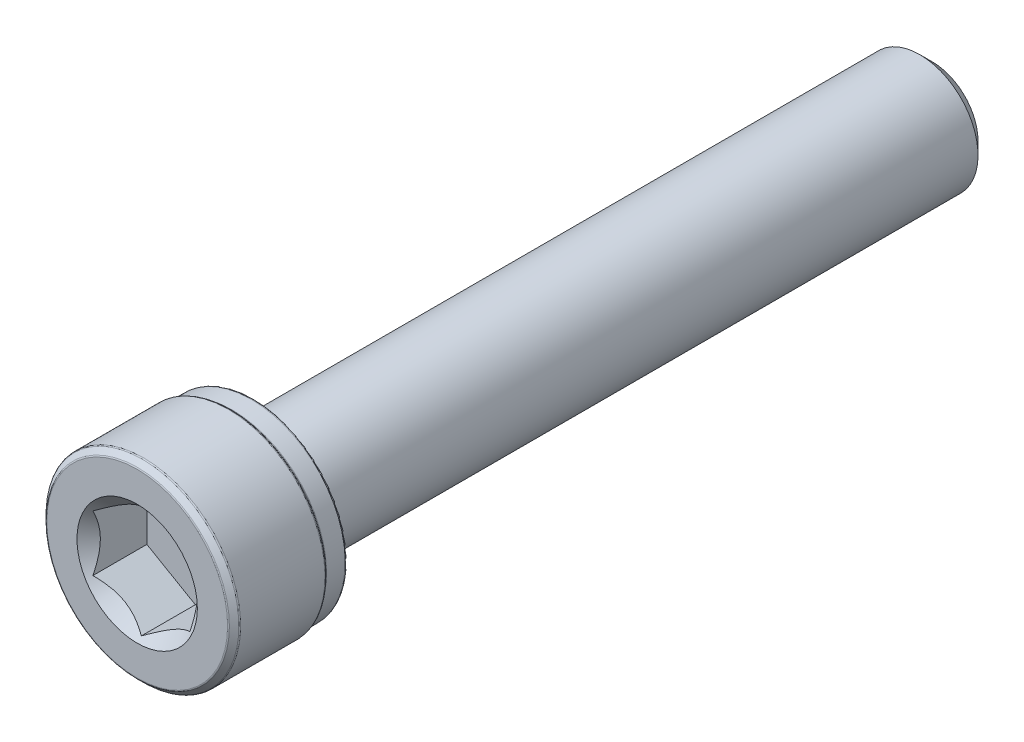
SolidWorks part; units mm, degrees
ref_plane "Front Plane" through (0, 0, 0) normal (0, 0, 1) x (1, 0, 0)
ref_plane "Top Plane" through (0, 0, 0) normal (0, 1, 0) x (1, 0, 0)
ref_plane "Right Plane" through (0, 0, 0) normal (1, 0, 0) x (0, 0, -1)
sketch "Sketch1" plane through (0, 0, 0) normal (1, 0, 0) x (0, 0, -1)
  line L0 (-20.5, 0) -> (20.5, 0) construction
  line L1 (20.5, 0) -> (20.5, 2.3505) construction
  line L2 (20.5, 2.3505) -> (19.8505, 3) construction
  line L3 (19.8505, 3) -> (19.75, 3) construction
  line L4 (19.75, 3) -> (-14.5, 3) construction
  line L5 (-14.5, 3) -> (-14.5, 5) construction
  line L6 (-14.5, 5) -> (-20.5, 5) construction
  line L7 (-20.5, 5) -> (-20.5, 0) construction
  line L8 (20.5, 2.3505) -> (20.5, 3) construction
  line L9 (20.4375, 3.1083) -> (20.9375, 2.2422) construction
  line L10 (20.9375, 2.2422) -> (21.4375, 3.1083) construction
  line L11 (21.4375, 3.1083) -> (20.4375, 3.1083) construction
  line L12 (20.9375, 3.1083) -> (20.9375, 3) construction
  line L13 (20.9375, 2.2422) -> (20.9375, 2.3505) construction
  line L14 (20.875, 2.3505) -> (21, 2.3505) construction
  line L15 (20.5, 3) -> (21.375, 3) construction
  line L16 (20.4688, 3.0541) -> (21.4062, 3.0541) construction
  line L17 (20.5, 0) -> (20.5, -3) construction
  line L18 (-14.8, 5) -> (-14.5, 4.7) construction
  line L19 (-20.2, 5) -> (-20.5, 4.7) construction
  line L20 (-14.5, 3) -> (-14.5, 0) construction
  line L21 (-14.5, 1.5) -> (-2.8333, 1.5) construction
  line L22 (-2.8333, 1.5) -> (8.8333, 1.5) construction
  line L23 (8.8333, 1.5) -> (20.5, 1.5) construction
  line L24 (-2.8333, 1.5) -> (-2.8333, 3) construction
  line L25 (-2.8333, 3) -> (-2.8333, 5) construction
  line L26 (8.8333, 1.5) -> (8.8333, 5) construction
  point P0 (-20.5, 2.5)
  point P3 (18, 3)
  point P4 (0, 0)
  point P18 (8.8333, 3)
  point P22 (20.9375, 2.3505)
  point P24 (19.75, 3)
  point P25 (20.9375, 3)
  point P28 (20.9375, 3.0541)
  point P29 (18, -3)
  point P30 (-2.8333, 3)
  point P31 (-17.5, 5)
  point P37 (-15.55, 5)
  point P38 (-20.05, 5)
  point P45 (-2.8333, 1.5)
  point P46 (8.8333, 1.5)
  dimension "D1" = 45
  dimension "D2" = 0.125
  dimension "D7" = 0.3
  dimension "D8" = 0.3
  dimension "D9" = 0.3
  dimension "D10" = 0.15
  dimension "D11" = 0.75
  dimension "Drive Size" = 5
  dimension "Head Diameter" = 10
  dimension "Head Height" = 6
  dimension "Thread Pitch" = 1
  dimension "Thread Dia" = 6
  dimension "Length" = 35
  dimension "D12" = 0.75
  dimension "D4" = 2.5
  dimension "Key Engagement" = 3
sketch "Sketch2" plane through (0, 0, 0) normal (1, 0, 0) x (0, 0, -1)
  line L0 (-20.5, 0) -> (-20.5, 4.6612)
  line L1 (-20.1612, 5) -> (-15.8138, 5)
  line L2 (-14.5, 4.725) -> (-14.5, 3.3)
  line L4 (19.8505, 3) -> (20.5, 2.3505)
  line L5 (20.5, 2.3505) -> (20.5, 0)
  line L6 (-14.5, 5) -> (-20.5, 5) construction
  line L7 (20.5, 0) -> (-20.5, 0)
  line L8 (-20.2, 5) -> (-20.5, 4.7) construction
  line L10 (-20.2275, 4.9725) -> (-20.4725, 4.7275)
  line L12 (-15.5862, 4.85) -> (-14.625, 4.85)
  line L14 (-14.8, 5) -> (-14.5, 4.7) construction
  line L15 (-15.7475, 4.9725) -> (-15.6525, 4.8775)
  line L17 (-14.5, 3) -> (-14.5, 5) construction
  line L19 (-14.2, 3) -> (19.8505, 3)
  line L20 (19.75, 3) -> (-14.5, 3) construction
  arc A0 (-14.625, 4.85) -> (-14.5, 4.725) centre (-14.625, 4.725) cw
  arc A1 (-14.5, 3.3) -> (-14.2, 3) centre (-14.2, 3.3) ccw
  arc A2 (-20.2275, 4.9725) -> (-20.1612, 5) centre (-20.1612, 4.9062) cw
  arc A3 (-20.4725, 4.7275) -> (-20.5, 4.6612) centre (-20.4062, 4.6612) ccw
  arc A4 (-15.7475, 4.9725) -> (-15.8138, 5) centre (-15.8138, 4.9062) ccw
  arc A5 (-15.6525, 4.8775) -> (-15.5862, 4.85) centre (-15.5862, 4.9438) ccw
  point P22 (-14.65, 4.85)
  point P37 (-15.625, 4.85)
  dimension "D2" = 0.125
  dimension "D3" = 0.3
  dimension "D4" = 0.0938
  dimension "D1" = 1.125
revolve "Revolve1" add sketch "Sketch2" angle 360 about L7
sketch "Sketch3" plane through (0, 0, 20.5) normal (0, 0, 1) x (1, 0, 0)
  line L1 (2.5, -1.4434) -> (2.5, 1.4434)
  line L2 (2.5, 1.4434) -> (0, 2.8868)
  line L3 (0, 2.8868) -> (-2.5, 1.4434)
  line L4 (-2.5, 1.4434) -> (-2.5, -1.4434)
  line L5 (-2.5, -1.4434) -> (0, -2.8868)
  line L6 (0, -2.8868) -> (2.5, -1.4434)
  circle A0 centre (0, 0) radius 2.5 construction
  circle A1 centre (0, 0) radius 5 construction
  circle A2 centre (0, 0) radius 5 construction
  circle A3 centre (0, 0) radius 2.8868 construction
  dimension "D1" = 5.7735
extrude "Cut-Extrude1" cut sketch "Sketch3" against normal up to vertex (3 mm away) up to point (0, 5, 17.5)
sketch "Sketch4" plane through (0, 0, 20.5) normal (0, 0, 1) x (1, 0, 0)
  circle A0 centre (0, 0) radius 3.1033
  dimension "D1" = 6.2065
extrude "Cut-Extrude2" cut sketch "Sketch4" against normal up to vertex (3 mm away) draft 45 up to point (0, 5, 17.5)
sketch "Sketch6" [suppressed] plane through (0, 0, -20.5) normal (0, 0, -1) x (-1, 0, 0)
  circle A0 centre (0, 0) radius 3
curve "Helix/Spiral1" [suppressed] pitch 1 height 36 turns 36
sketch "Sketch7" [suppressed] plane through (0, 0, 0) normal (1, 0, 0) x (0, 0, -1)
  line L0 (20.4688, 3.0541) -> (21.4062, 3.0541)
  line L1 (21.4062, 3.0541) -> (21, 2.3505)
  line L2 (21, 2.3505) -> (20.875, 2.3505)
  line L3 (20.875, 2.3505) -> (20.4688, 3.0541)
sweep "Cut-Sweep1" [suppressed] cut profiles "Sketch7" path "Helix/Spiral1"
sketch "Sketch8" [suppressed] plane through (0, 0, 0) normal (1, 0, 0) x (0, 0, -1)
  line L0 (-17.5, 0) -> (-17.5, 3.3)
  line L1 (-17.5, 1.4434) -> (-17.5, 2.8868) construction
  line L2 (-14.2, 3) -> (-14, 3)
  line L3 (-14.5, 3.3) -> (-17.5, 3.3)
  line L4 (-14, 3) -> (-12.2679, 0)
  line L5 (-12.2679, 0) -> (-17.5, 0)
  line L7 (-20.5, 0) -> (20.5, 0) construction
  line L8 (-14.5, 3) -> (-14.5, 5) construction
  arc A0 (-14.5, 3.3) -> (-14.2, 3) centre (-14.2, 3.3) ccw construction
  arc A1 (-14.5, 3.3) -> (-14.2, 3) centre (-14.2, 3.3) ccw
  dimension "D1" = 60
  dimension "D2" = 0.5
revolve "Revolve2" [suppressed] add sketch "Sketch8" angle 360 about L5
sketch "Sketch9" [suppressed] plane through (0, 0, 20.5) normal (0, 0, 1) x (1, 0, 0)
  line L0 (-0.0228, 4.9009) -> (-0.125, 5.1291)
  line L1 (-0.125, 5.1291) -> (0.125, 5.1291)
  line L2 (0.125, 5.1291) -> (0.0228, 4.9009)
  line L3 (0, 5) -> (0, 4.7) construction
  line L4 (0, 0) -> (-0.125, 5.1291) construction
  line L5 (0.125, 5.1291) -> (0, 0) construction
  circle A0 centre (0, 0) radius 4.85 construction
  arc A4 (-0.0228, 4.9009) -> (0.0228, 4.9009) centre (0, 4.9112) ccw
  point P10 (0, 4.85)
  point P19 (0, 4.85)
  dimension "D2" = 0.025
  dimension "D1" = 0.25
  dimension "D3" = 2.792
extrude "Cut-Extrude3" [suppressed] cut sketch "Sketch9" against normal through all
pattern_circular "CirPattern1" [suppressed] count 80 over 360 of bodies 112
equation "\"D2@Sketch1\" = \"Thread Pitch@Sketch1\" / 8"
equation "\"D4@Helix/Spiral1\" = \"Thread Pitch@Sketch1\""
equation "\"D7@Sketch1\" = \"Head Height@Sketch1\" * .05"
equation "\"D8@Sketch1\"=\"D7@Sketch1\""
equation "\"D9@Sketch1\"=\"D7@Sketch1\""
equation "\"D10@Sketch1\"=\"D7@Sketch1\"/2"
equation "\"D11@Sketch1\"=\"D10@Sketch1\"*5"
equation "\"D4@Sketch1\"=\"Thread Pitch@Sketch1\"*2.5"
equation "\"D12@Sketch1\"=\"Thread Pitch@Sketch1\"*.75"
equation "\"D3@Helix/Spiral1\"=\"Length@Sketch1\"+\"Thread Pitch@Sketch1\""
equation "\"D1@Sketch2\"=\"Head Height@Sketch1\"*0.1875"
equation "\"D2@Sketch2\"=\"Head Diameter@Sketch1\"*0.0125"
equation "\"D3@Sketch2\"=\"Thread Dia@Sketch1\"*0.05"
equation "\"D1@Sketch9\"=\"Head Diameter@Sketch1\"*0.025"
equation "\"D2@Sketch9\"=\"D1@Sketch9\"*0.1"
equation "\"D2@Sketch8\"=\"Thread Pitch@Sketch1\"*00.5"
equation "\"D4@Sketch2\"=\"D8@Sketch1\"*0.3125"
equation "\"D1@CirPattern1\"=int ((360/\"D3@Sketch9\")*0.625)"
equation "\"D1@Sketch4\"=\"D1@Sketch3\" * 01.075"
